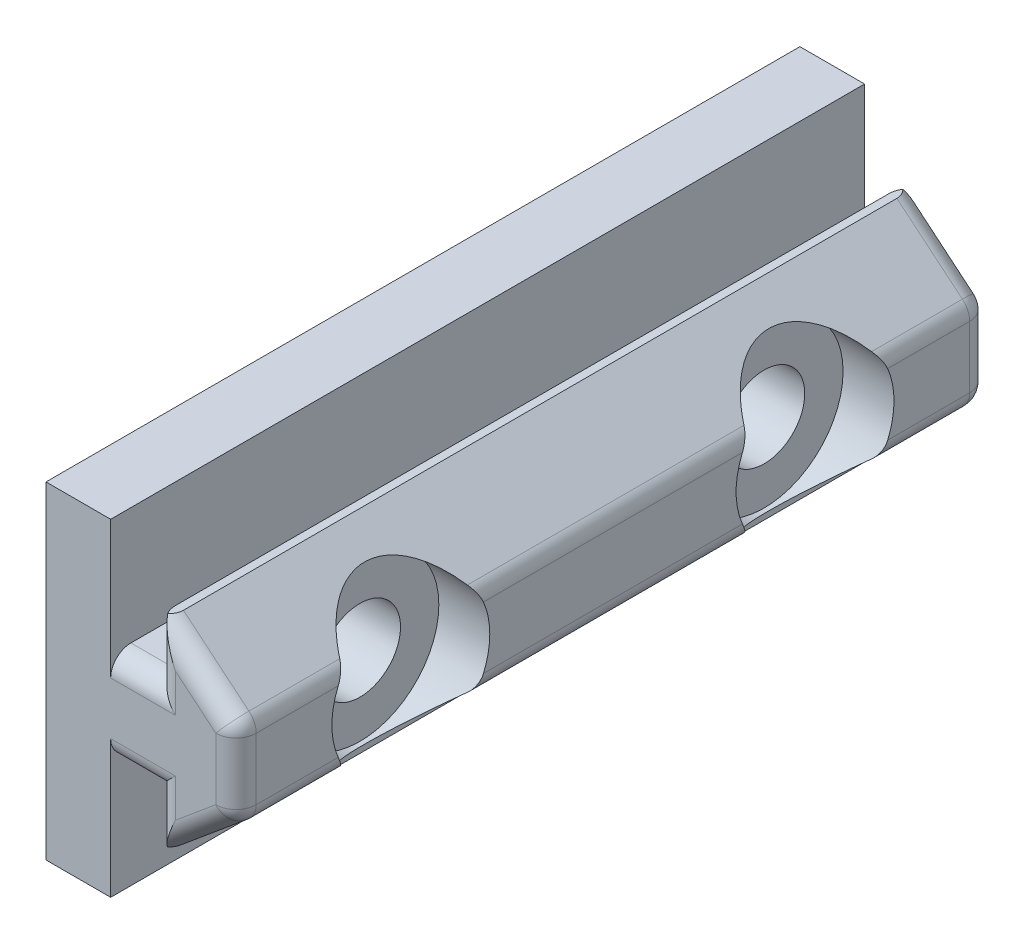
SolidWorks part; units mm, degrees
ref_plane "Front Plane" through (0, 0, 0) normal (0, 0, 1) x (1, 0, 0)
ref_plane "Top Plane" through (0, 0, 0) normal (0, 1, 0) x (1, 0, 0)
ref_plane "Right Plane" through (0, 0, 0) normal (1, 0, 0) x (0, 0, -1)
ref_plane "Plane1" through (0, 0, 23.6855) normal (0, 0, 1) x (1, 0, 0)
sketch "Sketch1" plane through (0, 0, 23.6855) normal (0, 0, 1) x (1, 0, 0)
  line L0 (3.302, 6.35) -> (-4.064, 6.35)
  line L1 (-4.064, 6.35) -> (-4.064, -6.35)
  line L2 (-4.064, -6.35) -> (3.302, -6.35)
  line L3 (3.302, -6.35) -> (7.874, -2.54)
  line L4 (7.874, -2.54) -> (7.874, 2.54)
  line L5 (7.874, 2.54) -> (3.302, 6.35)
extrude "Boss-Extrude1" add sketch "Sketch1" against normal blind 47.371
sketch "Sketch2" plane through (0, 0, 23.6855) normal (0, 0, 1) x (1, 0, 0)
  line L0 (-4.064, 6.35) -> (-4.064, 2.921)
  line L1 (-4.064, 2.921) -> (2.794, 2.921)
  line L2 (2.794, 2.921) -> (2.794, 6.35)
  line L3 (2.794, 6.35) -> (-4.064, 6.35)
extrude "Cut-Extrude1" cut sketch "Sketch2" against normal through all
sketch "Sketch3" plane through (0, 2.921, 0) normal (0, 1, 0) x (-1, 0, 0)
  line L0 (4.064, -23.6855) -> (0, -23.6855)
  line L1 (0, -23.6855) -> (0, 23.6855)
  line L2 (0, 23.6855) -> (4.064, 23.6855)
  line L3 (4.064, 23.6855) -> (4.064, -23.6855)
extrude "Boss-Extrude2" add sketch "Sketch3" along normal blind 7.366
sketch "Sketch4" plane through (0, 0, 23.6855) normal (0, 0, 1) x (1, 0, 0)
  line L0 (-4.064, -6.35) -> (2.794, -6.35)
  line L1 (2.794, -6.35) -> (2.794, -2.921)
  line L2 (2.794, -2.921) -> (-4.064, -2.921)
  line L3 (-4.064, -2.921) -> (-4.064, -6.35)
extrude "Cut-Extrude2" cut sketch "Sketch4" against normal through all
sketch "Sketch5" plane through (0, -2.921, 0) normal (0, -1, 0) x (1, 0, 0)
  line L0 (0, -23.6855) -> (-4.064, -23.6855)
  line L1 (-4.064, -23.6855) -> (-4.064, 23.6855)
  line L2 (-4.064, 23.6855) -> (0, 23.6855)
  line L3 (0, 23.6855) -> (0, -23.6855)
extrude "Boss-Extrude3" add sketch "Sketch5" along normal blind 7.366
hole_wizard "#3 Clearance Hole1" positions "Sketch7" profile "Sketch6" hole size "#3" standard "ANSI Inch"
sketch "Sketch7" plane through (-4.064, 0, 0) normal (-1, 0, 0) x (0, 0, 1)
  point P0 (12.7, 0)
  point P1 (-12.7, 0)
sketch "Sketch6" plane through (-4.064, 0, 12.7) normal (0, 1, 0) x (0, 0, 1)
  line L0 (0, 0) -> (0, 11.938)
  line L1 (0, 11.938) -> (1.3843, 11.938)
  line L2 (1.3843, 11.938) -> (1.3843, 0)
  line L5 (1.3843, 0) -> (0, 0)
  line L11 (0, -6.35) -> (0, 107.95) construction
  dimension "Thru Hole Dia." = 2.7686
  dimension "Thru Hole Depth" = 11.938
sketch "Sketch12" plane through (7.874, 0, 0) normal (1, 0, 0) x (0, 0, -1)
  line L0 (-12.7, 1.3843) -> (-12.7, -1.3843) construction
  line L1 (12.7, 1.3843) -> (12.7, -1.3843) construction
  circle A0 centre (-12.7, 0) radius 1.3843 construction
  circle A1 centre (12.7, 0) radius 1.3843 construction
  point P5 (-12.7, 0)
  point P11 (12.7, 0)
hole_wizard "CBORE for #10 Button Head Cap Screw1" positions "Sketch13" profile "Sketch14" counterbore size "#10" standard "ANSI Inch" end condition through all
sketch "Sketch13" plane through (7.874, 0, 0) normal (1, 0, 0) x (0, 0, -1)
  point P0 (-12.7, 0)
  point P3 (12.7, 0)
sketch "Sketch14" plane through (7.874, 0, 12.7) normal (0, 1, 0) x (0, 0, -1)
  line L0 (0, 0) -> (0, 11.938)
  line L1 (0, 11.938) -> (2.5527, 11.938)
  line L3 (2.5527, 11.938) -> (2.5527, 3.2004)
  line L4 (2.5527, 3.2004) -> (4.9606, 3.2004)
  line L5 (4.9606, 3.2004) -> (4.9606, 0)
  line L7 (4.9606, 0) -> (0, 0)
  line L11 (0, -6.35) -> (0, 107.95) construction
  dimension "Thru Hole Dia." = 5.1054
  dimension "Thru Hole Depth" = 11.938
  dimension "C'Bore Dia." = 9.9212
  dimension "C'Bore Depth" = 3.2004
fillet "Fillet1" radius 1.27 6 edges at (7.874, -2.54, 20.3233) (7.874, -2.54, -20.3233) (7.874, -2.54, 0) (7.874, 2.54, 20.3233) (7.874, 2.54, 0) (7.874, 2.54, -20.3233)
fillet "Fillet3" radius 1.27 9 edges at (5.3595, -4.6354, -23.6855) (7.7541, -2.4838, -23.6855) (5.3595, 4.6354, -23.6855) (7.7541, 2.4838, -23.6855) (1.397, -2.921, -23.6855) (1.397, 2.921, -23.6855) (2.794, 4.6355, -23.6855) (2.794, -4.6355, -23.6855) (7.874, 0, -23.6855)
fillet "Fillet5" radius 1.27 9 edges at (5.3595, -4.6354, 23.6855) (7.7541, -2.4838, 23.6855) (5.3595, 4.6354, 23.6855) (7.7541, 2.4838, 23.6855) (2.794, 4.6355, 23.6855) (1.397, 2.921, 23.6855) (1.397, -2.921, 23.6855) (2.794, -4.6355, 23.6855) (7.874, 0, 23.6855)
